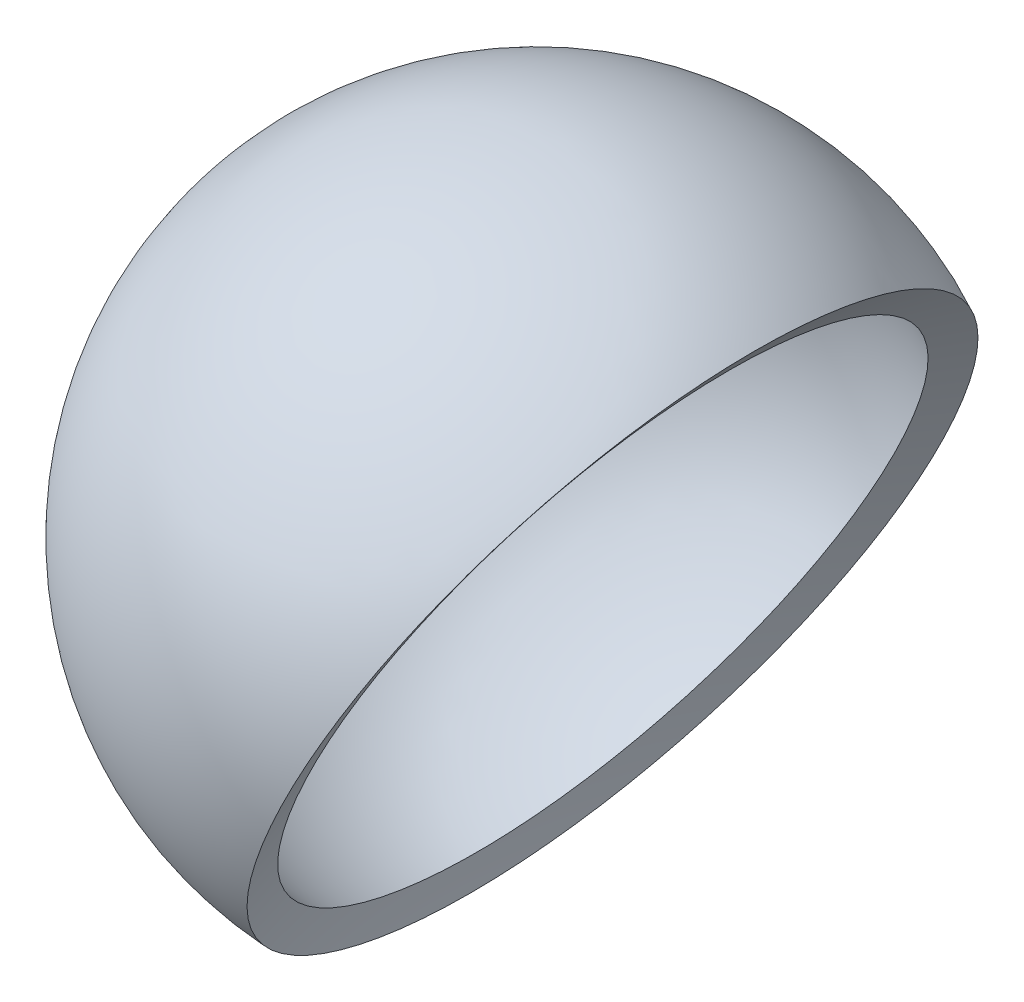
SolidWorks part; units mm, degrees
ref_plane "Front Plane" through (0, 0, 0) normal (0, 0, 1) x (1, 0, 0)
ref_plane "Top Plane" through (0, 0, 0) normal (0, 1, 0) x (1, 0, 0)
ref_plane "Right Plane" through (0, 0, 0) normal (1, 0, 0) x (0, 0, -1)
sketch "Sketch1" plane through (0, 0, 0) normal (0, 0, 1) x (1, 0, 0)
  line L0 (0, -45) -> (0, 45)
  arc A0 (0, 45) -> (0, -45) centre (0, 0) ccw
  arc A1 (0, 40) -> (0, -40) centre (0, 0) ccw
  dimension "D1" = 90
  dimension "D2" = 80
revolve "Revolve1" add sketch "Sketch1" angle 360 about L0 region at (-43.9938, 0, 0)
sketch "Sketch2" plane through (0, 0, 0) normal (0, 0, 1) x (1, 0, 0)
  line L0 (140, -65) -> (140, 85)
  line L1 (140, -65) -> (140, -215)
  arc A0 (140, 85) -> (140, -215) centre (140, -65) ccw
  dimension "D1" = 300
  dimension "D3" = 85
  dimension "D2" = 140
revolve "Cut-Revolve2" cut sketch "Sketch2" angle 360 about L0
